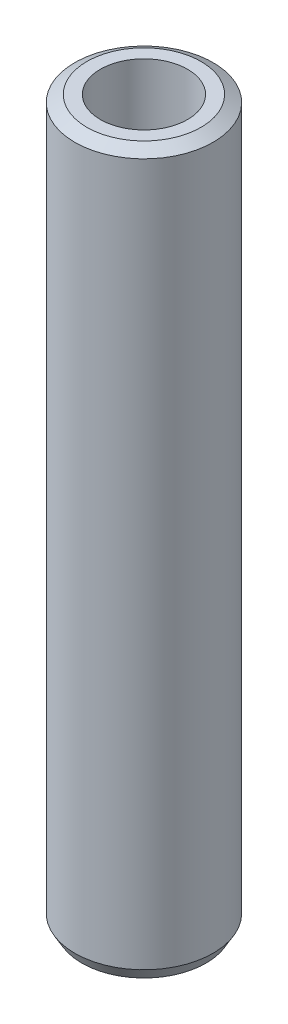
SolidWorks part; units mm, degrees
ref_plane "Front Plane" through (0, 0, 0) normal (0, 0, 1) x (1, 0, 0)
ref_plane "Top Plane" through (0, 0, 0) normal (0, 1, 0) x (1, 0, 0)
ref_plane "Right Plane" through (0, 0, 0) normal (1, 0, 0) x (0, 0, -1)
sketch "Sketch1" plane through (0, 0, 0) normal (0, 1, 0) x (1, 0, 0)
  circle A0 centre (0, 0) radius 57.5
  dimension "SHAFT_OD" = 115
extrude "Boss-Extrude1" add sketch "Sketch1" along normal blind 600
sketch "Sketch2" plane through (0, 0, 0) normal (0, 1, 0) x (1, 0, 0)
  circle A0 centre (0, 0) radius 36.2742
  dimension "BORE_D" = 72.5485
extrude "Cut-Extrude1" cut sketch "Sketch2" along normal through all
chamfer "Chamfer1" distance 5.7904 angle 60 2 edges at (0, 600, 57.5) (0, 0, 57.5) first distance on face at (0, 600, 57.5) first distance on face at (0, 0, 36.2742)
